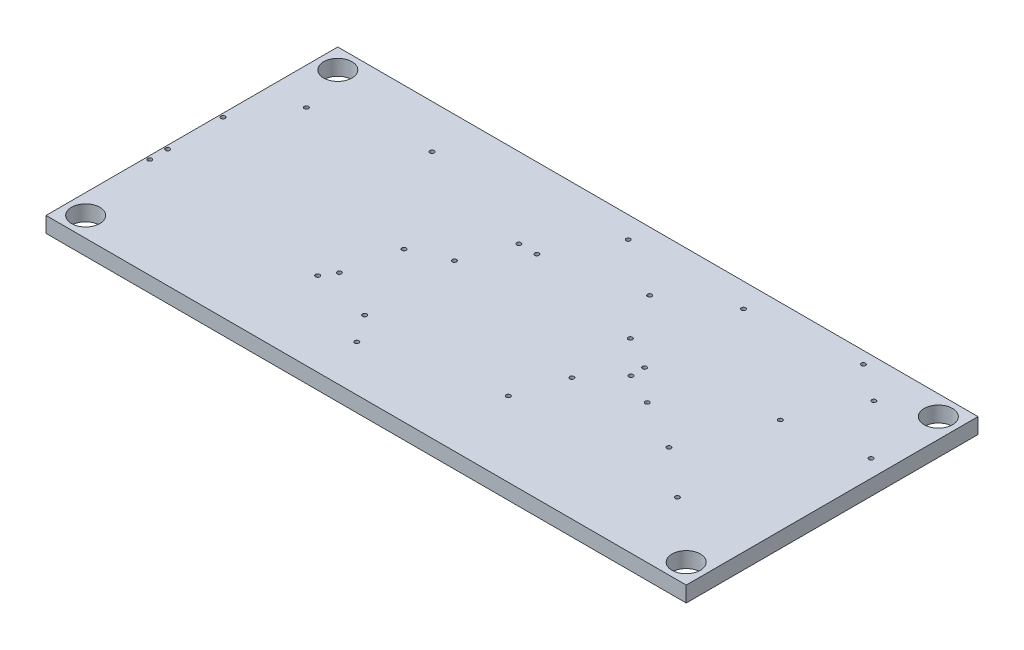
SolidWorks part; units mm, degrees
other "Camera2"
other "Camera3"
other "Camera5"
other "Camera6"
ref_plane "Front Plane" through (0, 0, 0) normal (0, 0, 1) x (1, 0, 0)
ref_plane "Top Plane" through (0, 0, 0) normal (0, 1, 0) x (1, 0, 0)
ref_plane "Right Plane" through (0, 0, 0) normal (1, 0, 0) x (0, 0, -1)
sketch "Sketch1" plane through (0, 0, 0) normal (0, 1, 0) x (1, 0, 0)
  line L1 (22.6, -10.3) -> (-22.6, -10.3)
  line L2 (22.6, -10.3) -> (22.6, 10.3)
  line L3 (22.6, 10.3) -> (-22.6, 10.3)
  line L4 (-22.6, -10.3) -> (-22.6, 10.3)
  line L5 (22.6, -10.3) -> (-22.6, 10.3) construction
  line L6 (22.6, 10.3) -> (-22.6, -10.3) construction
  point P0 (0, 0)
  dimension "D1" = 45.2
  dimension "D2" = 20.6
extrude "Boss-Extrude1" add sketch "Sketch1" along normal blind 1.1
sketch "Sketch18" plane through (0, 1.1, 0) normal (0, 1, 0) x (1, 0, 0)
  line L0 (22.6, 10.3) -> (-22.6, 10.3) construction
  line L2 (22.6, -10.3) -> (22.6, 10.3) construction
  line L4 (-22.6, -10.3) -> (22.6, -10.3) construction
  line L5 (-22.6, 10.3) -> (-22.6, -10.3) construction
  circle A0 centre (-21.2, -8.9) radius 1
  circle A1 centre (21.2, 8.9) radius 1
  point P3 (21.2, 9.9)
  point P4 (22.2, 8.9)
  point P16 (-22.2, -8.9)
  point P19 (-21.2, -9.9)
  dimension "D1" = 2
  dimension "D2" = 0.4
  dimension "D3" = 0.4
  dimension "D4" = 0.4
  dimension "D5" = 0.4
extrude "Cut-Extrude4" cut sketch "Sketch18" against normal through all
ref_plane "Plane3" through (0, -0.15, 0) normal (0, -1, 0) x (-1, 0, 0)
sketch "Sketch30" plane through (0, 0, 0) normal (0, -1, 0) x (1, 0, 0)
  circle A0 centre (-9.3331, 4.3877) radius 0.15
  circle A1 centre (-8.7445, 3.4491) radius 0.15
  circle A2 centre (4.7599, 5.0151) radius 0.15
  circle A3 centre (16.923, 5.2474) radius 0.15
  circle A4 centre (7.8306, -1.5279) radius 0.15
  circle A5 centre (7.8521, -0.5489) radius 0.15
  circle A6 centre (5.5498, -2.8081) radius 0.15
  circle A7 centre (5.8833, 1.6566) radius 0.15
  circle A8 centre (15.8275, -3.1155) radius 0.15
  circle A9 centre (21.3759, -3.9691) radius 0.15
  circle A10 centre (17.9615, -7.5844) radius 0.15
  circle A11 centre (15.356, -9.4499) radius 0.15
  circle A12 centre (3.5992, -6.1194) radius 0.15
  circle A13 centre (7.7403, -8.604) radius 0.15
  circle A14 centre (-0.5709, -8.7784) radius 0.15
  circle A15 centre (-2.9017, -4.6563) radius 0.15
  circle A16 centre (-4.1765, -4.6563) radius 0.15
  circle A17 centre (-5.4156, -1.349) radius 0.15
  circle A18 centre (-7.9014, -0.2789) radius 0.15
  circle A19 centre (-5.255, 5.1458) radius 0.15
  circle A20 centre (-3.8953, 7.0643) radius 0.15
  circle A21 centre (13.5745, 2.4948) radius 0.15
  circle A22 centre (10.0609, 0.5122) radius 0.15
  circle A23 centre (-12.8703, -7.2236) radius 0.15
  circle A24 centre (-20.0039, -5.4912) radius 0.15
  circle A25 centre (-22.3571, 3.2187) radius 0.15
  circle A26 centre (-22.3571, 1.9552) radius 0.15
  circle A27 centre (-22.3571, -1.9487) radius 0.15
  dimension "D1" = 0.3
extrude "Cut-Extrude6" cut sketch "Sketch30" against normal up to surface (1.1 mm away) up to face at (21.2, 1.1, -7.9)
mirror "Mirror1" about plane through (0, 0, 0) normal (1, 0, 0) of "Cut-Extrude4"
